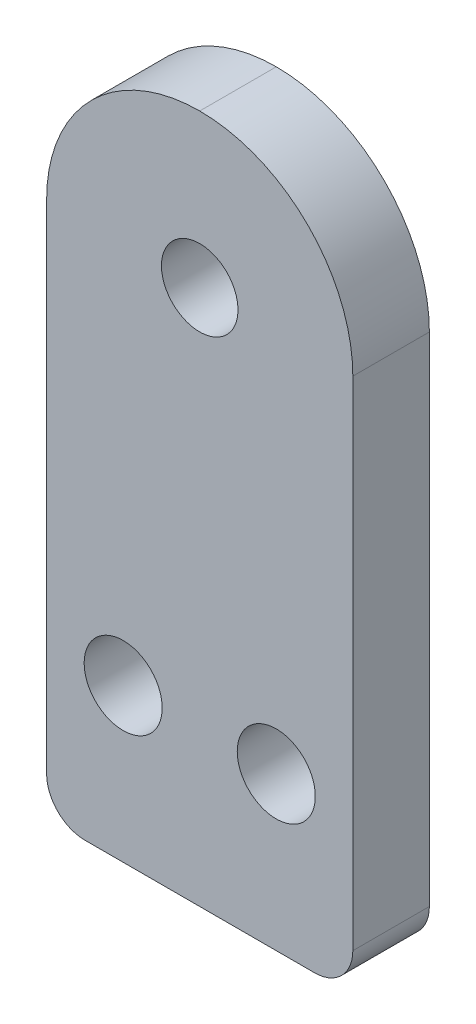
SolidWorks part; units mm, degrees
ref_plane "Front Plane" through (0, 0, 0) normal (0, 0, 1) x (1, 0, 0)
ref_plane "Top Plane" through (0, 0, 0) normal (0, 1, 0) x (1, 0, 0)
ref_plane "Right Plane" through (0, 0, 0) normal (1, 0, 0) x (0, 0, -1)
sketch "Sketch1" plane through (0, 0, 0) normal (0, 0, 1) x (1, 0, 0)
  line L1 (10, -22.5) -> (-10, -22.5)
  line L2 (10, -22.5) -> (10, 22.5)
  line L3 (10, 22.5) -> (-10, 22.5)
  line L4 (-10, -22.5) -> (-10, 22.5)
  line L5 (10, -22.5) -> (-10, 22.5) construction
  line L6 (10, 22.5) -> (-10, -22.5) construction
  point P0 (0, 0)
  dimension "D1" = 20
  dimension "D2" = 45
extrude "Boss-Extrude1" add sketch "Sketch1" along normal blind 5
fillet "Fillet2" radius 10 2 edges at (-10, 22.5, 2.5) (10, 22.5, 2.5)
sketch "Sketch2" plane through (0, 0, 0) normal (0, 0, -1) x (-1, 0, 0)
  circle A0 centre (0, 12.5) radius 2.5
  dimension "D1" = 5
extrude "Cut-Extrude1" cut sketch "Sketch2" against normal through all
sketch "Sketch3" plane through (0, 0, 0) normal (0, 0, -1) x (-1, 0, 0)
  line L0 (10, -22.5) -> (-10, -22.5) construction
  line L1 (10, 12.5) -> (10, -22.5) construction
  circle A0 centre (-5, -12.5) radius 2.55
  circle A1 centre (5, -12.5) radius 2.55
  dimension "D1" = 5.1
  dimension "D2" = 10
  dimension "D4" = 5.1
  dimension "D6" = 10
  dimension "D3" = 15
  dimension "D5" = 10
extrude "Cut-Extrude2" cut sketch "Sketch3" against normal blind 5
fillet "Fillet3" radius 2.5 2 edges at (-10, -22.5, 2.5) (10, -22.5, 2.5)
